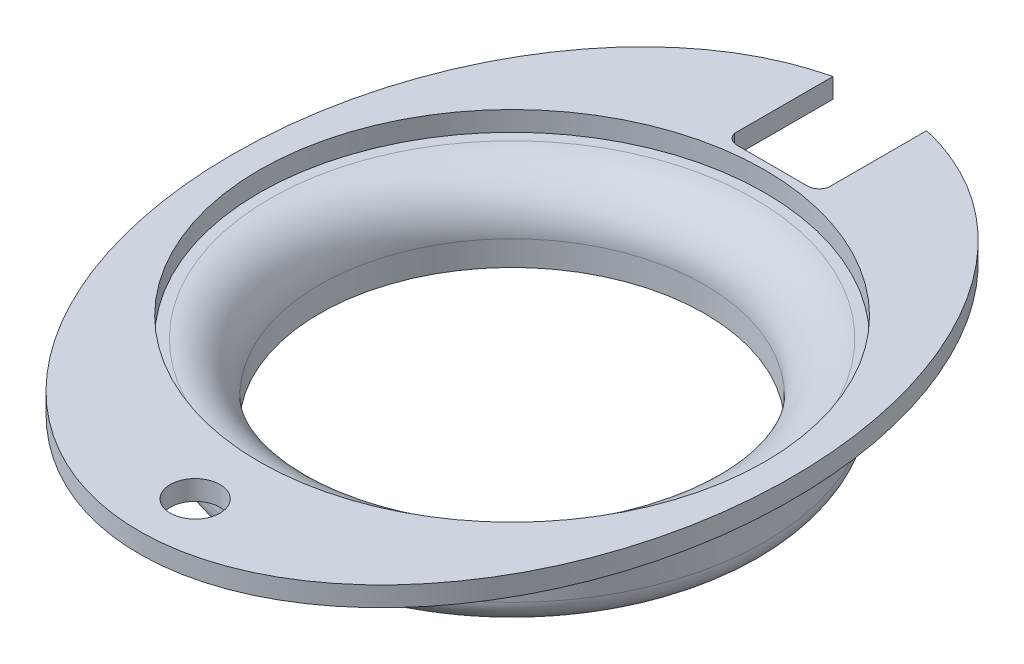
SolidWorks part; units mm, degrees
ref_plane "Front Plane" through (0, 0, 0) normal (0, 0, 1) x (1, 0, 0)
ref_plane "Top Plane" through (0, 0, 0) normal (0, 1, 0) x (1, 0, 0)
ref_plane "Right Plane" through (0, 0, 0) normal (1, 0, 0) x (0, 0, -1)
sketch "Sketch2" plane through (0, 0, 0) normal (0, 1, 0) x (1, 0, 0)
  line L0 (-3.7711, 29.5756) -> (-3.7711, 21.6756)
  line L1 (0, 41.7585) -> (0, 27.7685) construction
  line L2 (3.7711, 29.5756) -> (3.7711, 21.6756)
  line L3 (-2.664, 20.9325) -> (2.836, 20.9325)
  line L4 (-2.664, 20.9325) -> (-2.836, 20.9325)
  circle A1 centre (0, 0) radius 15.5
  circle A2 centre (0, 0) radius 20.335
  arc A3 (2.836, 20.9325) -> (3.7711, 21.6756) centre (2.836, 21.8925) ccw
  arc A4 (-2.836, 20.9325) -> (-3.7711, 21.6756) centre (-2.836, 21.8925) cw
  ellipse E0 centre (0, 0) end of major axis (0, -30) minor radius 22.5 (-3.7711, 29.5756) -> (3.7711, 29.5756) ccw
  point P18 (0.086, 20.9325)
  dimension "D1" = 60
  dimension "D2" = 31
  dimension "D4" = 40.67
  dimension "D6" = 0.96
  dimension "D3" = 45
  dimension "D5" = 5.5
  dimension "D7" = 0.086
  dimension "D8" = 3.7711
  dimension "D9" = 20.9325
extrude "Boss-Extrude1" add sketch "Sketch2" along normal blind 1.5875 contours L0 E0 L2 A3 L3 L4 A4 A2 region at (-4.5177, 0, -25.6256)
extrude "Boss-Extrude2" add sketch "Sketch2<4>" against normal blind 6 separate body contours A2 A1 | A1 region at (0, 0, 0) region at (-19.7598, 0, 0)
sketch "Sketch2<4>" plane through (0, 0, 0) normal (0, 1, 0) x (1, 0, 0) same geometry as "Sketch2"
sketch "Sketch3" plane through (0, 0, 0) normal (0, 1, 0) x (1, 0, 0)
  circle A0 centre (0, 0) radius 15.5
  dimension "D1" = 31
extrude "Cut-Extrude1" cut sketch "Sketch3" against normal blind 6
fillet "Fillet2" radius 4 1 edges at (0, 0, 15.5)
fillet "Fillet3" radius 2 1 edges at (0, -6, 20.335)
sketch "Sketch4" plane through (0, 1.5875, 0) normal (0, 1, 0) x (1, 0, 0)
  line L0 (0, 20.9325) -> (0, -11.5631) construction
  line L1 (-2.836, 20.9325) -> (2.836, 20.9325) construction
  line L2 (0, -30) -> (0, -25.5) construction
  circle A0 centre (0, -25.5) radius 2
  ellipse E0 centre (0, 0) end of major axis (0, -30) minor radius 22.5 (-3.7711, 29.5756) -> (3.7711, 29.5756) ccw construction
  dimension "D2" = 4
  dimension "D1" = 4.5
extrude "Cut-Extrude2" cut sketch "Sketch4" against normal through all both and the other way through all
